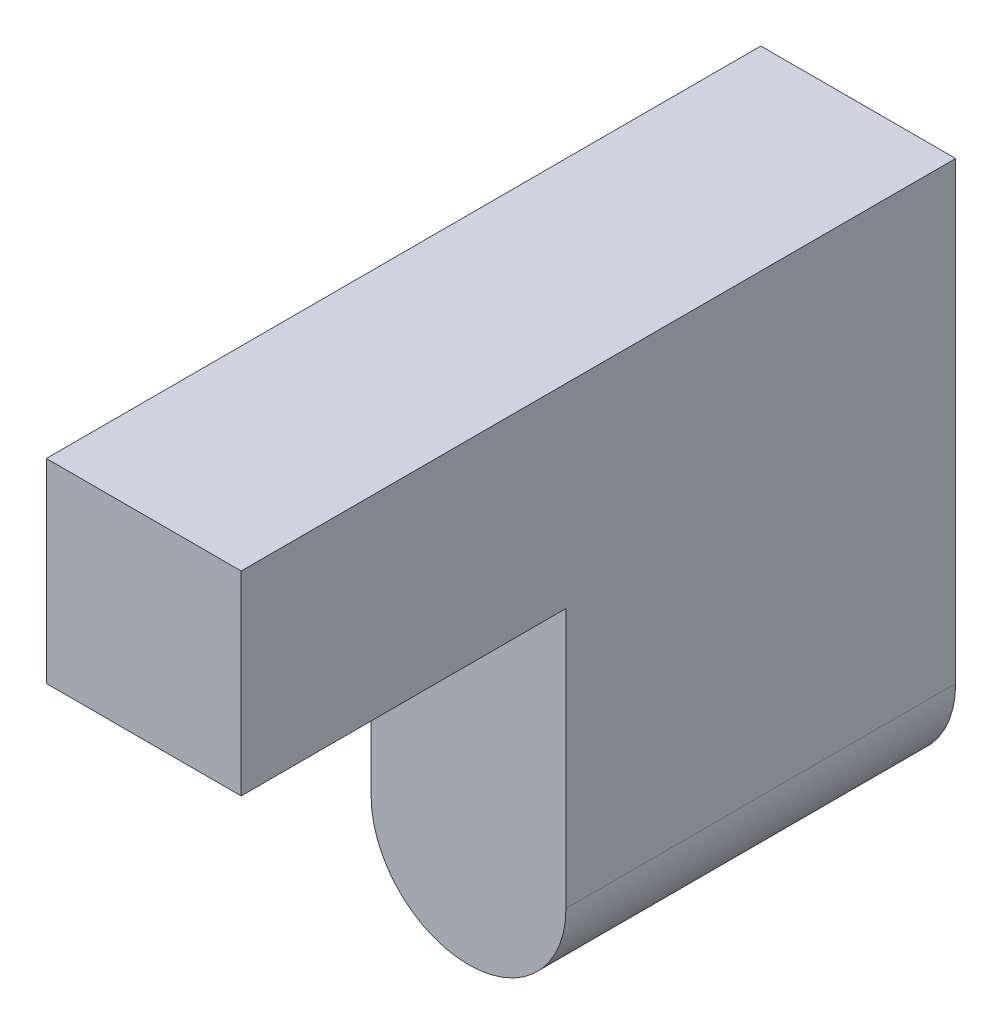
SolidWorks part; units mm, degrees
material "Plain Carbon Steel"
ref_plane "Front Plane" through (0, 0, 0) normal (0, 0, 1) x (1, 0, 0)
ref_plane "Top Plane" through (0, 0, 0) normal (0, 1, 0) x (1, 0, 0)
ref_plane "Right Plane" through (0, 0, 0) normal (1, 0, 0) x (0, 0, -1)
sketch "Sketch1" plane through (0, 0, 0) normal (0, 0, 1) x (1, 0, 0)
  line L0 (-1.5, 0.5) -> (1.5, 0.5)
  line L1 (-1.5, 3.5) -> (1.5, 3.5)
  line L2 (-1.5, 3.5) -> (-1.5, -3.5)
  line L4 (1.5, 3.5) -> (1.5, -3.5)
  line L5 (-1.5, 3.5) -> (1.5, -3.5) construction
  line L6 (-1.5, -3.5) -> (1.5, 3.5) construction
  arc A0 (1.5, -3.5) -> (-1.5, -3.5) centre (0, -3.5) cw
  point P0 (0, 0)
  point P7 (0, -5)
  dimension "D1" = 3
  dimension "D2" = 8.5
  dimension "D3" = 3
extrude "Boss-Extrude1" add sketch "Sketch1" along normal blind 6 contours A0 L4 L0 L2 region at (0, -2.0999, 0)
extrude "Boss-Extrude2" add sketch "Sketch1<3>" along normal blind 11 contours L4 L1 L2 L0 region at (0, 2, 0)
sketch "Sketch1<3>" plane through (0, 0, 0) normal (0, 0, 1) x (1, 0, 0) same geometry as "Sketch1"
